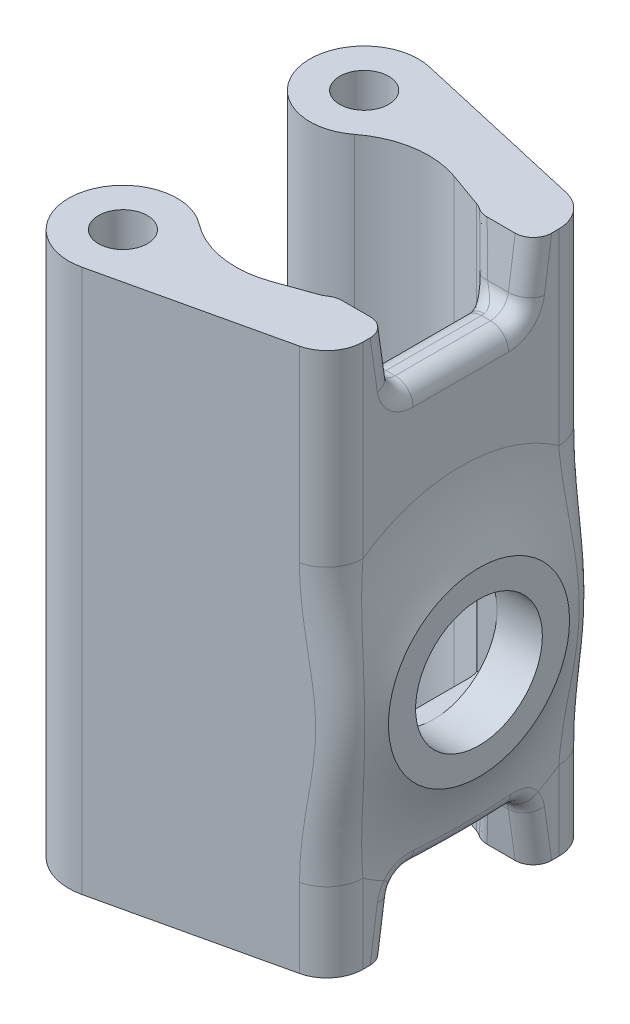
SolidWorks part; units mm, degrees
ref_plane "Ebene vorne" through (0, 0, 0) normal (0, 0, 1) x (1, 0, 0)
ref_plane "Ebene oben" through (0, 0, 0) normal (0, 1, 0) x (1, 0, 0)
ref_plane "Ebene rechts" through (0, 0, 0) normal (1, 0, 0) x (0, 0, -1)
sketch "Skizze1" plane through (0, 0, 0) normal (0, 1, 0) x (1, 0, 0)
  line L0 (0, 6.66) -> (0, 0) construction
  line L1 (0, 0) -> (0, -6.66) construction
  line L2 (0, 0) -> (12, 0) construction
  line L3 (12, -7) -> (12, 7)
  line L4 (12, 7) -> (0.6671, 9.5849)
  line L5 (9.5, -4) -> (9.5, 4)
  line L6 (9.5, 4) -> (2.9809, 6.322)
  line L7 (12, -7) -> (0.6671, -9.5849)
  line L8 (9.5, -4) -> (2.9809, -6.322)
  arc A0 (0.6671, 9.5849) -> (2.9809, 6.322) centre (0, 6.66) ccw
  arc A1 (2.9809, -6.322) -> (0.6671, -9.5849) centre (0, -6.66) ccw
  point P14 (9.5, 0)
  dimension "D2" = 6
  dimension "D1" = 13.32
  dimension "D3" = 4
  dimension "D4" = 12
  dimension "D5" = 2.5
  dimension "D6" = 14
  dimension "D7" = 8
extrude "Aufsatz-Linear austragen1" add sketch "Skizze1" along normal blind 30
sketch "Skizze2" plane through (12, 0, 0) normal (1, 0, 0) x (0, 0, -1)
  line L0 (0, 30) -> (0, 12) construction
  line L1 (-7, 30) -> (7, 30) construction
  circle A0 centre (0, 12) radius 3.5
  dimension "D1" = 7
  dimension "D2" = 18
extrude "Schnitt-Linear austragen1" cut sketch "Skizze2" against normal blind 17.5
sketch "Skizze3" plane through (9.5, 0, 0) normal (-1, 0, 0) x (0, 0, 1)
  line L1 (-3.5, 15.5) -> (3.5, 15.5)
  line L2 (-3.5, 15.5) -> (-3.5, 8.5)
  line L3 (-3.5, 8.5) -> (3.5, 8.5)
  line L4 (3.5, 15.5) -> (3.5, 8.5)
  line L5 (-3.5, 15.5) -> (3.5, 8.5) construction
  line L6 (-3.5, 8.5) -> (3.5, 15.5) construction
  point P0 (0, 12)
  dimension "D1" = 7
extrude "Schnitt-Linear austragen2" cut sketch "Skizze3" against normal blind 1
sketch "Skizze4" plane through (12, 0, 0) normal (1, 0, 0) x (0, 0, -1)
  circle A0 centre (0, 12) radius 3.5
  circle A1 centre (0, 12) radius 3.5 construction
  circle A2 centre (0, 12) radius 5
  dimension "D1" = 10
extrude "Aufsatz-Linear austragen2" add sketch "Skizze4" along normal blind 1
hole_wizard "Ø2.7 (2.7) Durchmesser Bohrung1" positions "Skizze7" profile "Skizze8" hole size "Ø2.7" standard "DIN"
sketch "Skizze7" plane through (0, 30, 0) normal (0, 1, 0) x (1, 0, 0)
  point P0 (0, -6.66)
  point P3 (0, 6.66)
sketch "Skizze8" plane through (0, 30, 6.66) normal (1, 0, 0) x (0, 0, 1)
  line L0 (0, 0) -> (0, 10.8112)
  line L1 (0, 10.8112) -> (1.35, 10)
  line L2 (1.35, 10) -> (1.35, 0)
  line L5 (1.35, 0) -> (0, 0)
  line L10 (0, 10.8112) -> (-1.35, 10) construction
  line L11 (0, -6.35) -> (0, 107.95) construction
  dimension "Bohrerdurchmesser" = 2.7
  dimension "Bohrungstiefe" = 10
  dimension "Spitzenwinkel" = 118
hole_wizard "Ø2.7 (2.7) Durchmesser Bohrung2" positions "Skizze10" profile "Skizze9" hole size "Ø2.7" standard "DIN"
sketch "Skizze10" plane through (0, 0, 0) normal (0, -1, 0) x (-1, 0, 0)
  point P0 (0, 6.66)
  point P3 (0, -6.66)
sketch "Skizze9" plane through (0, 0, -6.66) normal (1, 0, 0) x (0, 0, -1)
  line L0 (0, 0) -> (0, 10.8112)
  line L1 (0, 10.8112) -> (1.35, 10)
  line L2 (1.35, 10) -> (1.35, 0)
  line L5 (1.35, 0) -> (0, 0)
  line L10 (0, 10.8112) -> (-1.35, 10) construction
  line L11 (0, -6.35) -> (0, 107.95) construction
  dimension "Bohrerdurchmesser" = 2.7
  dimension "Bohrungstiefe" = 10
  dimension "Spitzenwinkel" = 118
fillet "Verrundung1" radius 10 1 edges at (12, 12, 5)
fillet "Verrundung2" radius 5 2 edges at (2.9809, 15, 6.322) (2.9809, 15, -6.322)
fillet "Verrundung3" radius 2 6 edges at (12, 2.894, -7) (12.0954, 15.8723, -6.9782) (12, 2.894, 7) (12.0954, 8.1277, 6.9782) (12, 24.106, -7) (12, 24.106, 7)
fillet "Verrundung4" radius 1.5 2 edges at (9.5, 15, 4) (9.5, 15, -4)
ref_plane "Ebene1" through (0, 15, 0) normal (0, 1, 0) x (1, 0, 0)
sketch "Skizze11" plane through (12, 0, 0) normal (1, 0, 0) x (0, 0, -1)
  line L0 (0, 30) -> (0, 0) construction
  line L1 (-5.4048, 30) -> (5.4048, 30) construction
  line L2 (3.5, 26.5) -> (-3.5, 26.5)
  line L3 (-3.5, 26.5) -> (-4, 30)
  line L4 (3.5, 26.5) -> (4, 30)
  line L5 (-4, 30) -> (4, 30)
  point P9 (0, 26.5)
  dimension "D1" = 8
  dimension "D2" = 7
  dimension "D3" = 3.5
extrude "Durchbruch Stromkabel" cut sketch "Skizze11" against normal up to next and the other way through all
mirror "Spiegeln1" about plane through (0, 15, 0) normal (0, 1, 0) of "Durchbruch Stromkabel"
fillet "Verrundung Stromkabel innen" radius 1 10 edges at (9.253, 28.3661, -3.7666) (9.253, 28.3661, 3.7666) (9.5, 26.5, 0) (10.6962, 26.5, 3.5) (10.6962, 26.5, -3.5) (10.6969, 3.5, 3.5) (10.6969, 3.5, -3.5) (9.253, 1.6339, 3.7666) (9.5, 3.5, 0) (9.253, 1.6339, -3.7666)
fillet "Verrundung Stromkabel aussen" radius 1 12 edges at (12, 28.6793, 3.8113) (12, 26.7445, 3.2879) (12, 26.5, 0) (12, 26.7445, -3.2879) (12, 28.6793, -3.8113) (12, 1.3207, 3.8113) (12.0035, 3.4226, 3.0186) (12.0046, 3.4436, -2.9637) (12, 1.3207, -3.8113) (12, 2.9704, 3.5152) (12, 2.9704, -3.5152)
